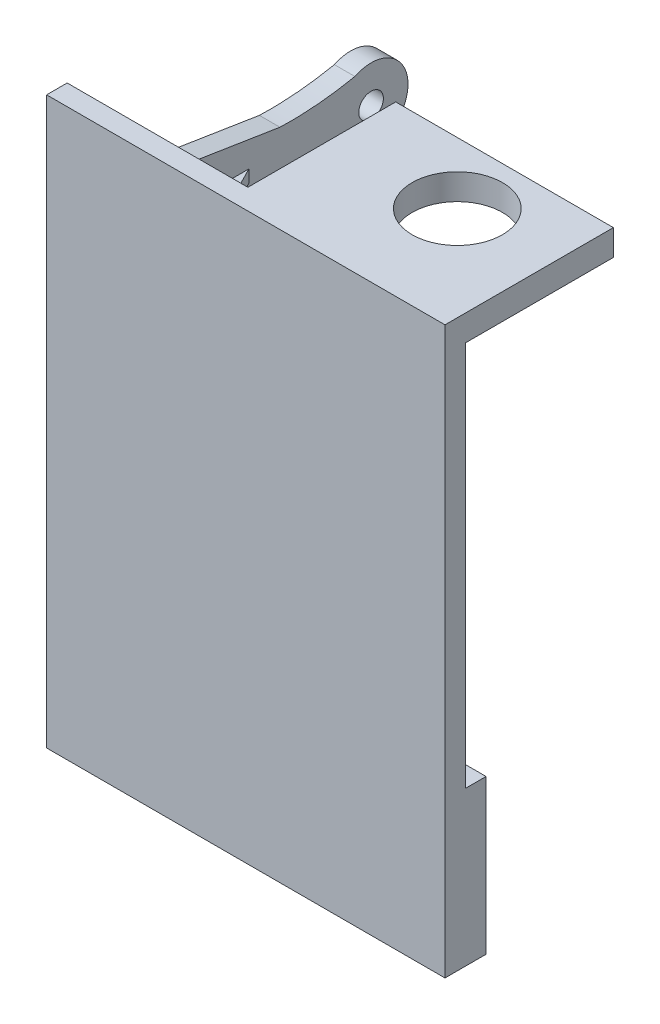
SolidWorks part; units mm, degrees
ref_plane "Plan de face" through (0, 0, 0) normal (0, 0, 1) x (1, 0, 0)
ref_plane "Plan de dessus" through (0, 0, 0) normal (0, 1, 0) x (1, 0, 0)
ref_plane "Plan de droite" through (0, 0, 0) normal (1, 0, 0) x (0, 0, -1)
sketch "Esquisse4" plane through (0, 0, 0) normal (0, 0, 1) x (1, 0, 0)
  line L1 (-23.5, 18.75) -> (23.5, 18.75)
  line L2 (-23.5, 18.75) -> (-23.5, -18.75)
  line L3 (-23.5, -18.75) -> (23.5, -18.75)
  line L4 (23.5, 18.75) -> (23.5, -18.75)
  line L5 (-23.5, 18.75) -> (23.5, -18.75) construction
  line L6 (-23.5, -18.75) -> (23.5, 18.75) construction
  point P0 (0, 0)
  dimension "D1" = 37.5
  dimension "D2" = 47
extrude "Boss.-Extru.2" add sketch "Esquisse4" along normal blind 10 contours L2 L3 L4 L1
sketch "Esquisse5" plane through (0, 0, 0) normal (0, 0, -1) x (-1, 0, 0)
  line L1 (-21.5, 16.75) -> (21.5, 16.75)
  line L2 (-21.5, 16.75) -> (-21.5, -16.75)
  line L3 (-21.5, -16.75) -> (21.5, -16.75)
  line L4 (21.5, 16.75) -> (21.5, -16.75)
  line L5 (-21.5, 16.75) -> (21.5, -16.75) construction
  line L6 (-21.5, -16.75) -> (21.5, 16.75) construction
  point P0 (0, 0)
  dimension "D1" = 43
  dimension "D2" = 33.5
extrude "Enlèv. mat.-Extru.1" cut sketch "Esquisse5" against normal blind 8
sketch "Esquisse6" plane through (0, -18.75, 0) normal (0, -1, 0) x (-1, 0, 0)
  line L0 (-23.5, -10) -> (-23.5, 0) construction
  line L1 (23.5, -10) -> (-23.5, -10)
  line L2 (23.5, -10) -> (23.5, -5)
  line L3 (23.5, -5) -> (-23.5, -5)
  line L4 (-23.5, -10) -> (-23.5, -5)
  dimension "D1" = 5
extrude "Boss.-Extru.3" add sketch "Esquisse6" against normal blind 137.74
sketch "Esquisse7" plane through (-23.5, 0, 0) normal (-1, 0, 0) x (0, 0, 1)
  line L1 (5, 118.99) -> (10, 118.99)
  line L2 (5, 118.99) -> (5, -18.75)
  line L3 (5, -18.75) -> (10, -18.75)
  line L4 (10, 118.99) -> (10, -18.75)
extrude "Boss.-Extru.4" add sketch "Esquisse7" along normal blind 50
sketch "Esquisse8" plane through (0, 0, 5) normal (0, 0, -1) x (-1, 0, 0)
  line L1 (73.5, 118.99) -> (34.1078, 118.99)
  line L2 (73.5, 118.99) -> (73.5, 41.3297)
  line L3 (73.5, 41.3297) -> (34.1078, 41.3297)
  line L4 (34.1078, 118.99) -> (34.1078, 41.3297)
  line L5 (-23.5, 118.99) -> (29.5, 118.99)
  line L6 (-23.5, 118.99) -> (-23.5, 112.69)
  line L7 (-23.5, 112.69) -> (29.5, 112.69)
  line L8 (29.5, 118.99) -> (29.5, 112.69)
  dimension "D1" = 53
  dimension "D2" = 6.3
extrude "Boss.-Extru.5" add sketch "Esquisse8" along normal blind 36 contours L6 L5 L8 L7
sketch "Esquisse9" plane through (0, 118.99, 0) normal (0, 1, 0) x (1, 0, 0)
  line L0 (23.5, 31) -> (-29.5, 31) construction
  line L1 (23.5, 31) -> (23.5, -10) construction
  circle A0 centre (0.5, 16) radius 11
  dimension "D1" = 15
  dimension "D2" = 23
extrude "Enlèv. mat.-Extru.4" cut sketch "Esquisse9" against normal blind 19 contours A0
sketch "Esquisse11" plane through (0, 0, 5) normal (0, 0, -1) x (-1, 0, 0)
  line L0 (73.5, 118.99) -> (29.5, 118.99) construction
  line L1 (73.5, 118.99) -> (68.5, 118.99)
  line L2 (73.5, 118.99) -> (73.5, 45.49)
  line L3 (73.5, 45.49) -> (68.5, 45.49)
  line L4 (68.5, 118.99) -> (68.5, 45.49)
  line L5 (73.5, 118.99) -> (73.5, -18.75) construction
  dimension "D1" = 73.5
  dimension "D2" = 5
extrude "Boss.-Extru.6" add sketch "Esquisse11" along normal blind 80
sketch "Esquisse12" plane through (-73.5, 0, 0) normal (-1, 0, 0) x (0, 0, 1)
  line L0 (-75, 45.49) -> (-75, 118.99) construction
  line L1 (10, 118.99) -> (-75, 118.99) construction
  circle A0 centre (-64, 82.24) radius 3
  dimension "D3" = 6
  dimension "D1" = 11
  dimension "D2" = 36.75
extrude "Enlèv. mat.-Extru.5" cut sketch "Esquisse12" against normal blind 70 contours A0
sketch "Esquisse16" plane through (-73.5, 0, 0) normal (-1, 0, 0) x (0, 0, 1)
  line L0 (-41.8106, 75.7214) -> (10, 67.5329)
  line L1 (10, -18.75) -> (10, 118.99) construction
  line L2 (-41.8106, 88.7586) -> (10, 96.9471)
  line L3 (5, 45.49) -> (10, 45.49)
  line L4 (5, 45.49) -> (5, 118.99)
  line L5 (10, 118.99) -> (-75, 118.99) construction
  line L6 (-64, 82.24) -> (-75, 81.98)
  line L7 (-75, 45.49) -> (-75, 118.99) construction
  line L11 (-64, 82.24) -> (5, 82.24) construction
  circle A0 centre (-64, 82.24) radius 9
  spline S0 degree 3 poles (-60.057, 74.1497) (-53.9583, 75.401) (-47.8762, 75.9249) (-41.8106, 75.7214) knots 0.095729 0.095729 0.095729 0.095729 0.540175 0.540175 0.540175 0.540175
  spline S1 degree 3 poles (-60.057, 90.3303) (-53.9583, 89.079) (-47.8762, 88.5551) (-41.8106, 88.7586) knots 0.095729 0.095729 0.095729 0.095729 0.540175 0.540175 0.540175 0.540175
  line M3 (10, 118.99) -> (-75, 118.99)
  line M4 (-75, 118.99) -> (-75, 45.49)
  line M5 (-75, 45.49) -> (5, 45.49)
extrude "Enlèv. mat.-Extru.6" cut sketch "Esquisse16" against normal blind 10 contours A0 L4 M3 M4 | A0 L4 M4 M5 region at (-73.5, 59.5998, -36.8739) region at (-73.5, 104.8706, -36.8896)
sketch "Sketch1" plane through (-68.5, 0, 0) normal (1, 0, 0) x (0, 0, -1)
  line L0 (-5, 83.74) -> (-5, 80.74) construction
  line L21 (35, 82.24) -> (61, 82.24) construction
  line L23 (35, 83.74) -> (-5, 83.74)
  line L24 (35, 83.74) -> (35, 80.74)
  line L25 (35, 80.74) -> (-5, 80.74)
  line L26 (-5, 83.74) -> (-5, 80.74)
  circle A0 centre (64, 82.24) radius 3 construction
  point P11 (15, 83.2629)
  point P12 (15, 82.24)
  dimension "D1" = 3
  dimension "D2" = 40
extrude "Boss-Extrude2" add sketch "Sketch1" along normal blind 20 contours L25 L26 L23 L24
chamfer "Chamfer2" distance 40 angle 27 1 edges at (-48.5, 82.24, -35) first distance on face at (-48.5, 82.24, -15)
